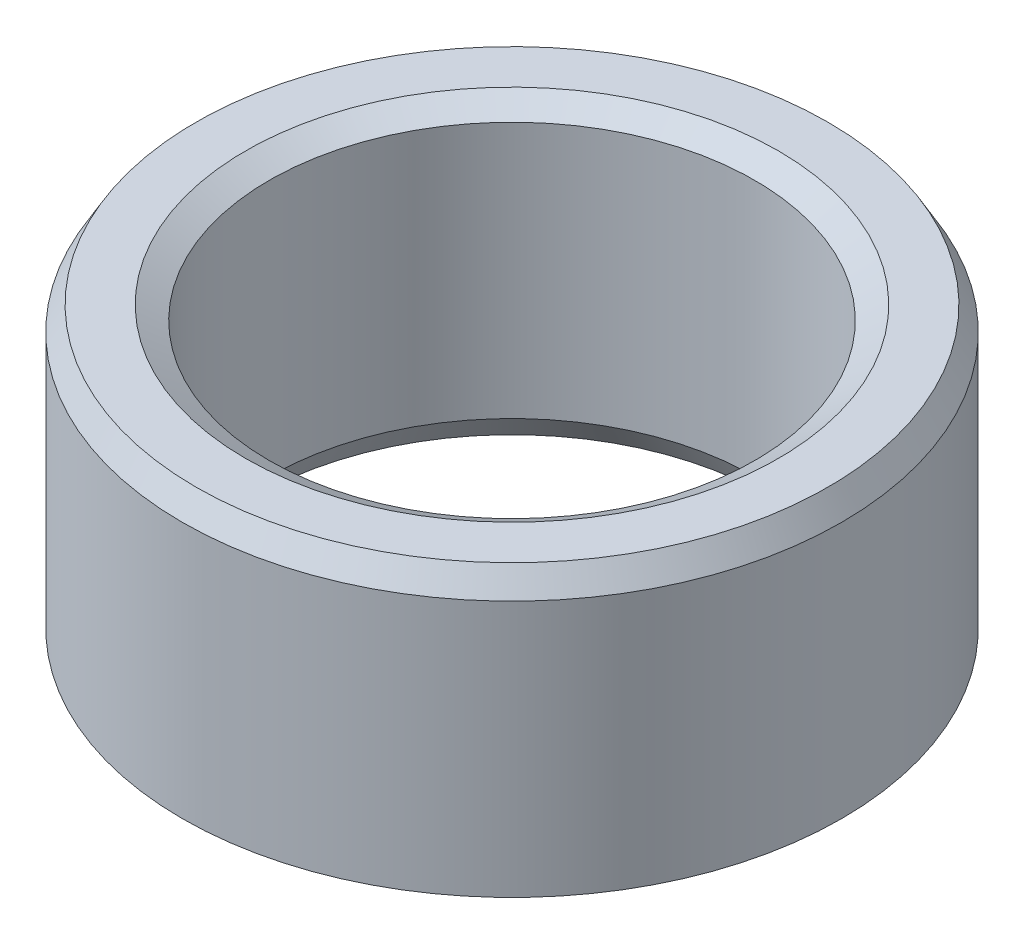
SolidWorks part; units mm, degrees
ref_plane "Front Plane" through (0, 0, 0) normal (0, 0, 1) x (1, 0, 0)
ref_plane "Top Plane" through (0, 0, 0) normal (0, 1, 0) x (1, 0, 0)
ref_plane "Right Plane" through (0, 0, 0) normal (1, 0, 0) x (0, 0, -1)
sketch "Sketch1" plane through (0, 0, 0) normal (0, 1, 0) x (1, 0, 0)
  circle A0 centre (0, 0) radius 40
  dimension "SLEEVE_OD" = 80
extrude "Boss-Extrude1" add sketch "Sketch1" along normal blind 35.6604
sketch "Sketch2" plane through (0, 0, 0) normal (0, 1, 0) x (1, 0, 0)
  circle A0 centre (0, 0) radius 29.4533
  dimension "BORE_D" = 58.9066
extrude "Cut-Extrude1" cut sketch "Sketch2" along normal through all
chamfer "Chamfer1" distance 2.8702 angle 30 4 edges at (0, 35.6604, 29.4533) (0, 0, 29.4533) (0, 0, 40) (0, 35.6604, 40) first distance on face at (0, 35.6604, 29.4533) first distance on face at (0, 0, 29.4533) first distance on face at (0, 35.6604, 40)
